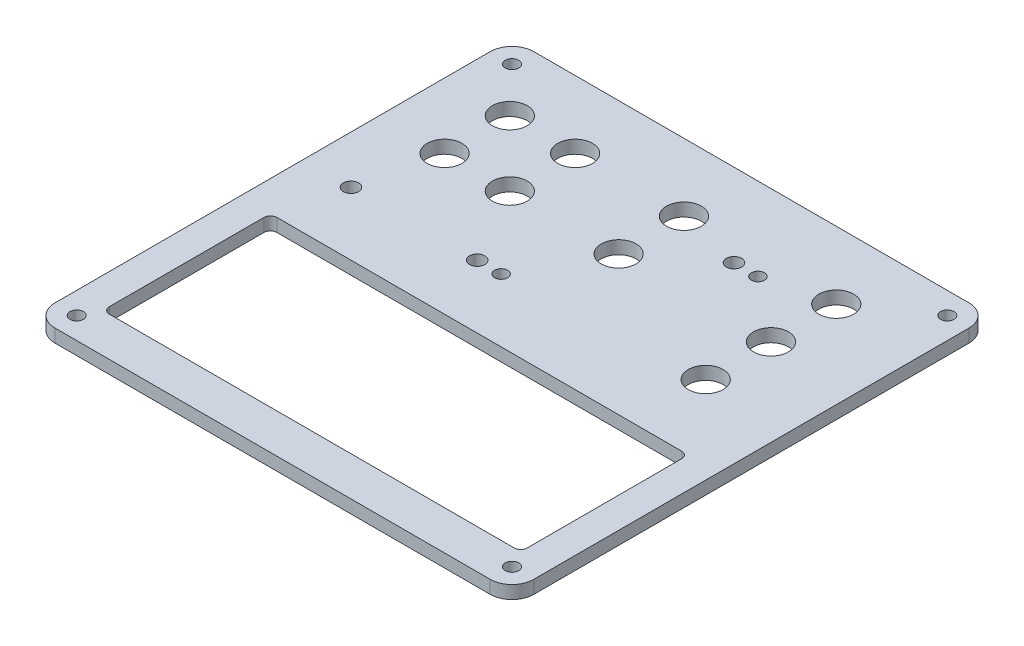
SolidWorks part; units mm, degrees
ref_plane "Front Plane" through (0, 0, 0) normal (0, 0, 1) x (1, 0, 0)
ref_plane "Top Plane" through (0, 0, 0) normal (0, 1, 0) x (1, 0, 0)
ref_plane "Right Plane" through (0, 0, 0) normal (1, 0, 0) x (0, 0, -1)
sketch "Sketch1" plane through (0, 0, 0) normal (0, 1, 0) x (1, 0, 0)
  line L1 (-55, 55) -> (55, 55)
  line L2 (-55, 55) -> (-55, -55)
  line L3 (-55, -55) -> (55, -55)
  line L4 (55, 55) -> (55, -55)
  line L5 (-55, 55) -> (55, -55) construction
  line L6 (-55, -55) -> (55, 55) construction
  circle A0 centre (-50, 50) radius 1.55
  circle A1 centre (50, 50) radius 1.55
  circle A2 centre (50, -50) radius 1.55
  circle A3 centre (-50, -50) radius 1.55
  point P0 (0, 0)
  dimension "D4" = 3.1
  dimension "D8" = 3.1
  dimension "D9" = 3.1
  dimension "D10" = 3.1
  dimension "D1" = 110
  dimension "D2" = 110
  dimension "D3" = 5
  dimension "D5" = 5
  dimension "D6" = 5
  dimension "D7" = 5
extrude "Boss-Extrude1" add sketch "Sketch1" along normal blind 3 contours A3 | A2 | A1 | A0 | L1 L4 L3 L2
fillet "Fillet1" radius 5 4 edges at (-55, 1.5, -55) (55, 1.5, -55) (55, 1.5, 55) (-55, 1.5, 55)
sketch "Sketch2" plane through (0, 3, 0) normal (0, 1, 0) x (1, 0, 0)
  line L0 (0, 55) -> (0, -55) construction
  line L1 (-48, -46) -> (48, -46)
  line L2 (-48, -46) -> (-48, -7.5)
  line L3 (-48, -7.5) -> (48, -7.5)
  line L4 (48, -46) -> (48, -7.5)
  line L5 (-50, 55) -> (50, 55) construction
  line L6 (-50, -55) -> (50, -55) construction
  line L7 (-55, 50) -> (-55, -50) construction
  line L8 (55, 50) -> (55, -50) construction
  dimension "D1" = 7
  dimension "D2" = 7
  dimension "D3" = 38.5
  dimension "D4" = 9
extrude "Cut-Extrude1" cut sketch "Sketch2" against normal through all contours L3 L4 L1 L2
fillet "Fillet2" radius 1.5 4 edges at (-48, 1.5, 46) (48, 1.5, 46) (48, 1.5, 7.5) (-48, 1.5, 7.5)
sketch "Sketch3" plane through (0, 3, 0) normal (0, 1, 0) x (1, 0, 0)
  line L0 (35, 55) -> (35, -55) construction
  line L1 (-55, 50) -> (-55, -50) construction
  line L2 (-55, 39.5) -> (55, 39.5) construction
  line L3 (55, 50) -> (55, -50) construction
  line L4 (-55, 24.5) -> (55, 24.5) construction
  line L5 (-55, 9.5) -> (55, 9.5) construction
  line L6 (-40, 55) -> (-40, -55) construction
  line L7 (-50, 55) -> (50, 55) construction
  line L8 (-50, -55) -> (50, -55) construction
  line L9 (-25, 55) -> (-25, -55) construction
  line L10 (0, 55) -> (0, -55) construction
  circle A0 centre (-40, 39.5) radius 4
  circle A1 centre (-40, 24.5) radius 4
  circle A3 centre (-25, 39.5) radius 4
  circle A4 centre (-25, 24.5) radius 4
  circle A5 centre (0, 39.5) radius 4
  circle A6 centre (0, 24.5) radius 4
  circle A7 centre (35, 39.5) radius 4
  circle A8 centre (35, 24.5) radius 4
  circle A9 centre (35, 9.5) radius 4
  dimension "D3" = 8
  dimension "D4" = 8
  dimension "D5" = 8
  dimension "D8" = 8
  dimension "D9" = 15
  dimension "D11" = 8
  dimension "D12" = 8
  dimension "D13" = 8
  dimension "D15" = 8
  dimension "D16" = 8
  dimension "D1" = 15
  dimension "D2" = 15.5
  dimension "D6" = 15
  dimension "D7" = 15
  dimension "D10" = 25
  dimension "D14" = 35
extrude "Cut-Extrude2" cut sketch "Sketch3" against normal through all contours A1 | A3 | A4 | A5 | A6 | A0 | A7 | A8 | A9 region at (-40, 3, -24.5) region at (-25, 3, -39.5) region at (-25, 3, -24.5) region at (0, 3, -39.5) region at (0, 3, -24.5)
sketch "Sketch4" plane through (0, 3, 0) normal (0, 1, 0) x (1, 0, 0)
  line L1 (-55, 50) -> (-55, -50) construction
  line L2 (55, 50) -> (55, -50) construction
  line L3 (-44, -55) -> (-44, 55) construction
  line L4 (-50, -55) -> (50, -55) construction
  line L5 (-50, 55) -> (50, 55) construction
  line L6 (-15, 55) -> (-15, -55) construction
  line L7 (-55, 7) -> (55, 7) construction
  line L8 (-55, 36) -> (55, 36) construction
  line L9 (15, 55) -> (15, -55) construction
  circle A0 centre (-44, 7) radius 1.75
  circle A1 centre (-15, 7) radius 1.75
  circle A2 centre (-9.5, 7) radius 1.5
  circle A3 centre (15, 36) radius 1.75
  circle A4 centre (20.5, 36) radius 1.5
  dimension "D3" = 3.5
  dimension "D4" = 40
  dimension "D6" = 3.5
  dimension "D8" = 3
  dimension "D9" = 3.5
  dimension "D10" = 3
  dimension "D1" = 11
  dimension "D5" = 62
  dimension "D7" = 5.5
  dimension "D11" = 5.5
  dimension "D12" = 40
  dimension "D13" = 19
extrude "Cut-Extrude3" cut sketch "Sketch4" against normal through all contours A0 | A1 | A2 | A3 | A4
